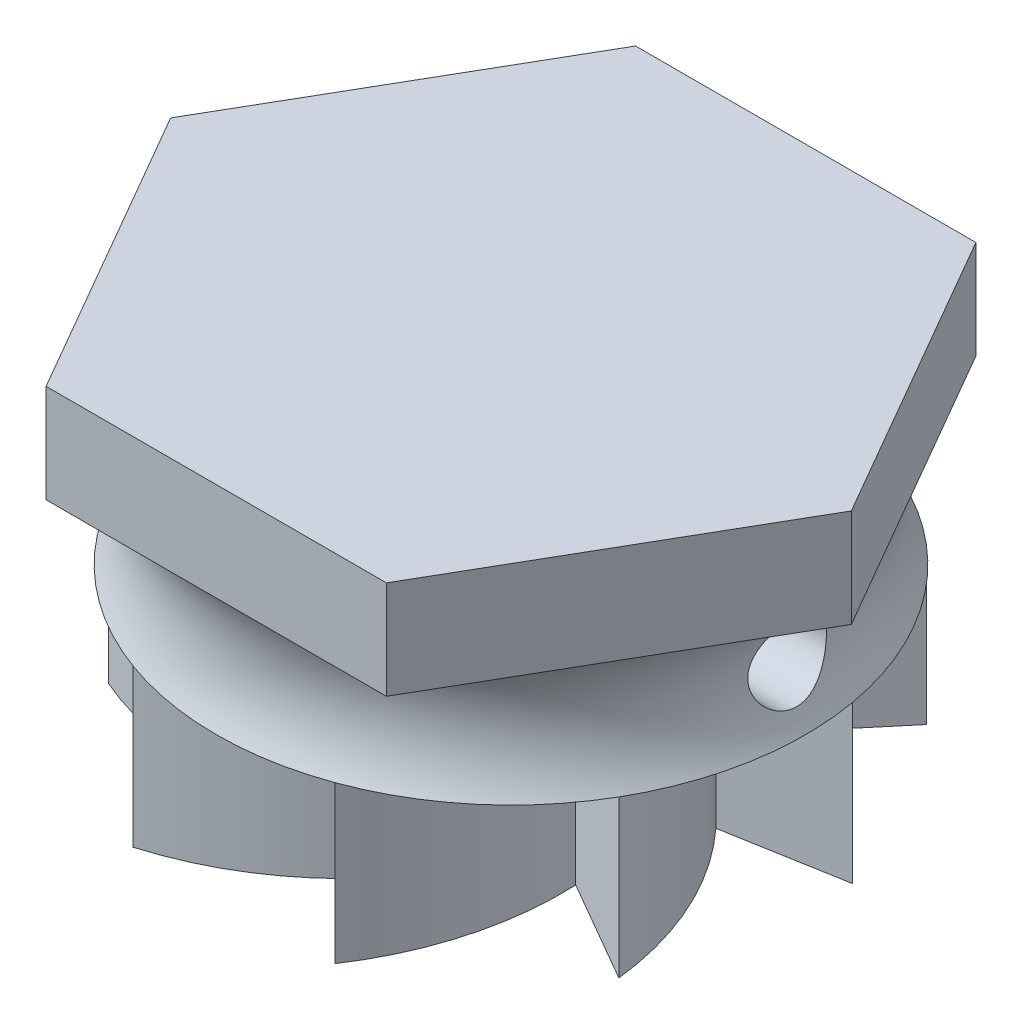
SolidWorks part; units mm, degrees
material "PLA"
ref_plane "Front Plane" through (0, 0, 0) normal (0, 0, 1) x (1, 0, 0)
ref_plane "Top Plane" through (0, 0, 0) normal (0, 1, 0) x (1, 0, 0)
ref_plane "Right Plane" through (0, 0, 0) normal (1, 0, 0) x (0, 0, -1)
sketch "Sketch1" plane through (0, 0, 0) normal (0, 1, 0) x (1, 0, 0)
  line L0 (0, -1000) -> (0, 49000) construction
  line L1 (0, 4.5) -> (0, 7.5)
  line L2 (0, 0) -> (-2.8925, 3.4472) construction
  line L5 (2.8925, 3.4472) -> (4.8209, 5.7453)
  line L8 (4.4316, 0.7814) -> (7.3861, 1.3024)
  line L11 (3.8971, -2.25) -> (6.4952, -3.75)
  line L14 (1.5391, -4.2286) -> (2.5652, -7.0477)
  line L17 (-1.5391, -4.2286) -> (-2.5652, -7.0477)
  line L20 (-3.8971, -2.25) -> (-6.4952, -3.75)
  line L23 (-4.4316, 0.7814) -> (-7.3861, 1.3024)
  line L26 (-2.8925, 3.4472) -> (-4.8209, 5.7453)
  circle A0 centre (0, 0) radius 3.025
  circle A1 centre (0, 0) radius 4.5 construction
  arc A18 (-2.8925, 3.4472) -> (0, 7.5) centre (4.742, 1.0569) cw
  arc A19 (0, 4.5) -> (4.8209, 5.7453) centre (4.312, -2.2385) cw
  arc A20 (2.8925, 3.4472) -> (7.3861, 1.3024) centre (1.8643, -4.4864) cw
  arc A21 (4.4316, 0.7814) -> (6.4952, -3.75) centre (-1.4557, -4.6352) cw
  arc A22 (3.8971, -2.25) -> (2.5652, -7.0477) centre (-4.0946, -2.615) cw
  arc A23 (1.5391, -4.2286) -> (-2.5652, -7.0477) centre (-4.8175, 0.6287) cw
  arc A24 (-1.5391, -4.2286) -> (-6.4952, -3.75) centre (-3.2863, 3.5782) cw
  arc A25 (-3.8971, -2.25) -> (-7.3861, 1.3024) centre (-0.2174, 4.8535) cw
  arc A26 (-4.4316, 0.7814) -> (-4.8209, 5.7453) centre (2.9532, 3.8578) cw
  point P46 (0, 0)
  point P54 (0, 0)
  point P56 (0, 0)
  point P85 (0, 0)
  dimension "D1" = 6.05
  dimension "D2" = 7.5
  dimension "D5" = 8
  dimension "D3" = 3
  dimension "D4" = 40
  dimension "D6" = 9
extrude "Boss-Extrude1" add sketch "Sketch1" along normal blind 4 contours A26 L23 A25 L20 A24 L17 A23 L14 A22 L11 A21 L8 A20 L5 A19 L1 A18 L26 A0 region at (2.363, 0, -5.3065)
sketch "Sketch2" plane through (0, 4, 0) normal (0, 1, 0) x (1, 0, 0)
  circle A0 centre (0, 0) radius 7.5
extrude "Boss-Extrude2" add sketch "Sketch2" along normal blind 3 and the other way blind 0.01
sketch "Sketch3" plane through (0, 7, 0) normal (0, 1, 0) x (1, 0, 0)
  line L1 (4.3301, 7.5) -> (-4.3301, 7.5)
  line L2 (-4.3301, 7.5) -> (-8.6603, 0)
  line L3 (-8.6603, 0) -> (-4.3301, -7.5)
  line L4 (-4.3301, -7.5) -> (4.3301, -7.5)
  line L5 (4.3301, -7.5) -> (8.6603, 0)
  line L6 (8.6603, 0) -> (4.3301, 7.5)
  circle A0 centre (0, 0) radius 7.5 construction
  circle A2 centre (0, 0) radius 7.5 construction
extrude "Boss-Extrude3" add sketch "Sketch3" along normal blind 2.5
sketch "Sketch4" plane through (0, 0, 0) normal (1, 0, 0) x (0, 0, -1)
  line L0 (0, -1000) -> (0, 49000) construction
  line L1 (-3.75, 3.99) -> (1.3024, 3.99) construction
  circle A0 centre (0, 5.49) radius 1
  dimension "D1" = 2
  dimension "D2" = 1.5
extrude "Cut-Extrude1" cut sketch "Sketch4" against normal through all both and the other way through all
sketch "Sketch5" plane through (0, 0, 0) normal (1, 0, 0) x (0, 0, -1)
  line L0 (7.5, 7) -> (7.5, 3.99)
  arc A0 (7.5, 7) -> (7.5, 3.99) centre (10.0952, 5.495) ccw
  dimension "D1" = 3
sweep "Cut-Sweep1" cut profiles "Sketch5" path "Sketch2<2>"
sketch "Sketch2<2>" plane through (0, 4, 0) normal (0, 1, 0) x (1, 0, 0) same geometry as "Sketch2"
